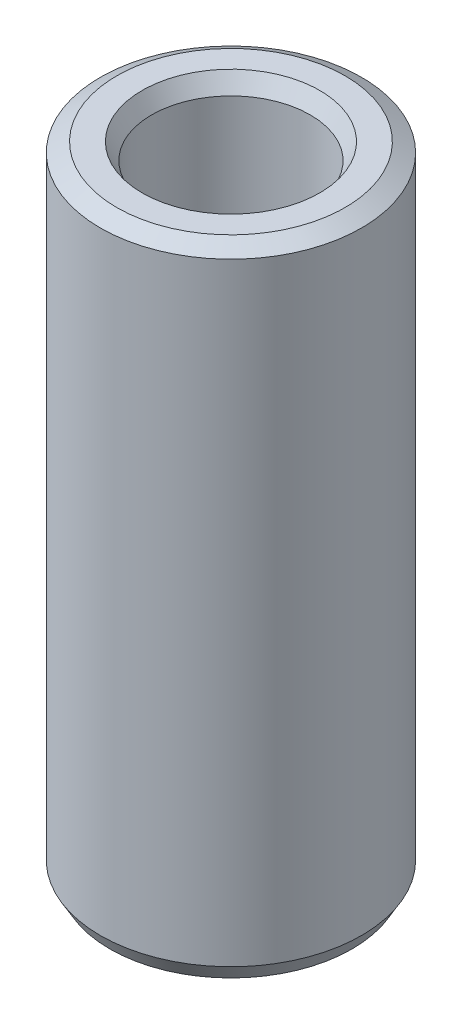
SolidWorks part; units mm, degrees
ref_plane "Front Plane" through (0, 0, 0) normal (0, 0, 1) x (1, 0, 0)
ref_plane "Top Plane" through (0, 0, 0) normal (0, 1, 0) x (1, 0, 0)
ref_plane "Right Plane" through (0, 0, 0) normal (1, 0, 0) x (0, 0, -1)
sketch "Sketch1" plane through (0, 0, 0) normal (0, 1, 0) x (1, 0, 0)
  circle A0 centre (0, 0) radius 35
  dimension "SLEEVE_OD" = 70
extrude "Boss-Extrude1" add sketch "Sketch1" along normal blind 171.1753
sketch "Sketch2" plane through (0, 0, 0) normal (0, 1, 0) x (1, 0, 0)
  circle A0 centre (0, 0) radius 21.2599
  dimension "BORE_D" = 42.5198
extrude "Cut-Extrude1" cut sketch "Sketch2" along normal through all
chamfer "Chamfer1" distance 2.5418 angle 60 4 edges at (0, 171.1753, 21.2599) (0, 0, 21.2599) (0, 0, 35) (0, 171.1753, 35) first distance on face at (0, 171.1753, 21.2599) first distance on face at (0, 0, 21.2599) first distance on face at (0, 171.1753, 35)
